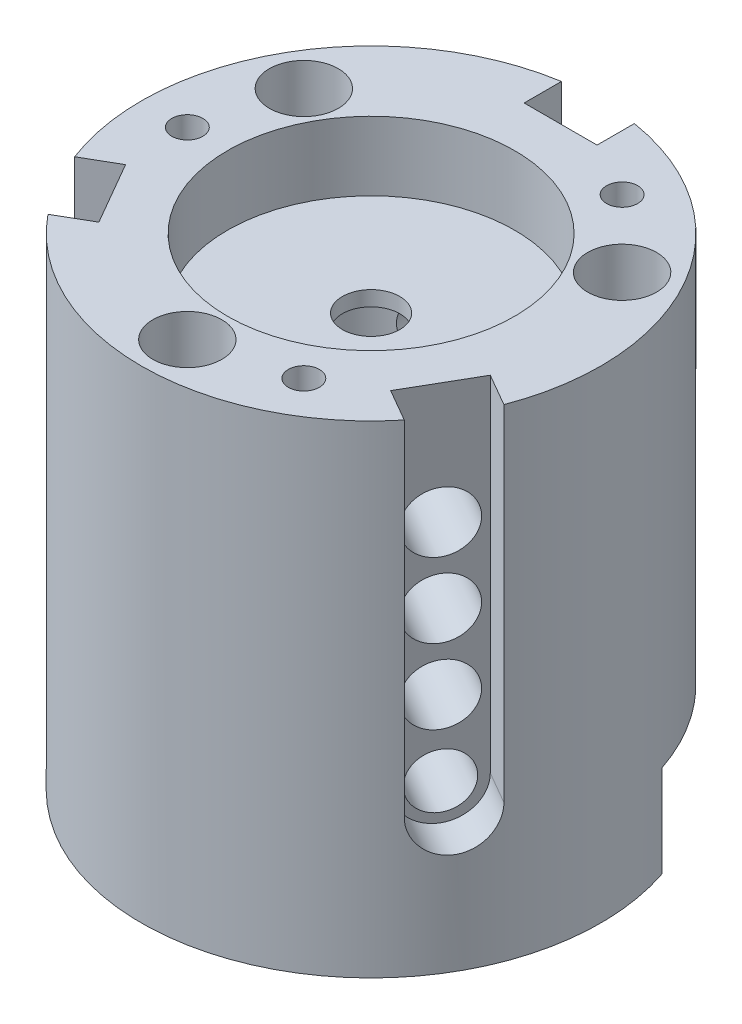
SolidWorks part; units mm, degrees
ref_plane "Front Plane" through (0, 0, 0) normal (0, 0, 1) x (1, 0, 0)
ref_plane "Top Plane" through (0, 0, 0) normal (0, 1, 0) x (1, 0, 0)
ref_plane "Right Plane" through (0, 0, 0) normal (1, 0, 0) x (0, 0, -1)
sketch "Sketch1" plane through (0, 0, 0) normal (0, 1, 0) x (1, 0, 0)
  circle A0 centre (0, 0) radius 20
  dimension "D1" = 40
extrude "Boss-Extrude1" add sketch "Sketch1" along normal blind 42
sketch "Sketch2" plane through (0, 0, 0) normal (0, 1, 0) x (1, 0, 0)
  circle A0 centre (0, 0) radius 5.5
  dimension "D1" = 11
extrude "Cut-Extrude1" cut sketch "Sketch2" along normal blind 35
sketch "Sketch3" plane through (0, 42, 0) normal (0, 1, 0) x (1, 0, 0)
  circle A1 centre (0, -16) radius 3
  circle A2 centre (-13.8564, 8) radius 3
  circle A3 centre (13.8564, 8) radius 3
  point P7 (0, 0)
  dimension "D1" = 3
  dimension "D3" = 6
  dimension "D2" = 16
extrude "Cut-Extrude2" cut sketch "Sketch3" against normal blind 20
sketch "Sketch4" plane through (0, 42, 0) normal (0, 1, 0) x (1, 0, 0)
  circle A0 centre (0, 0) radius 2.5
  dimension "D1" = 5
extrude "Cut-Extrude3" cut sketch "Sketch4" against normal through all
sketch "Sketch6" plane through (0, 42, 0) normal (0, 1, 0) x (1, 0, 0)
  line L0 (8, 13.8564) -> (0, 0) construction
  line L1 (0, 0) -> (0, 12.1298) construction
  circle A0 centre (8, 13.8564) radius 1.3525
  circle A1 centre (8, -13.8564) radius 1.3525
  circle A2 centre (-16, 0) radius 1.3526
  point P12 (0, 0)
  dimension "D3" = 2.7051
  dimension "D1" = 30
  dimension "D2" = 16
  dimension "D4" = 3
extrude "Cut-Extrude5" cut sketch "Sketch6" against normal blind 10
ref_axis "Axis1" through (0, -2, 0) along (0, 1, 0)
ref_plane "Plane1" through (0, 0, 0) normal (0.866, 0, -0.5) x (0, 1, 0)
ref_plane "Plane2" through (-17.3205, 0, 10) normal (0.866, 0, -0.5) x (0, 1, 0)
sketch "Sketch8" plane through (-17.3205, 0, 10) normal (0.866, 0, -0.5) x (0, 1, 0)
  line L0 (-2, 0) -> (42, 0) construction
  line L1 (42, -20) -> (42, 20) construction
  line L2 (42, 0) -> (12, 0) construction
  line L3 (42, -3.175) -> (12, -3.175)
  line L4 (42, 3.175) -> (12, 3.175)
  arc A1 (42, -3.175) -> (42, 3.175) centre (42, 0) ccw
  arc A2 (12, 3.175) -> (12, -3.175) centre (12, 0) ccw
  point P6 (27, 0)
  dimension "D1" = 3.175
  dimension "D2" = 0
  dimension "D3" = 30
extrude "Cut-Extrude6" cut sketch "Sketch8" along normal blind 3.5
sketch "Sketch9" plane through (-14.2894, 0, 8.25) normal (-0.866, 0, 0.5) x (0.5, 0, 0.866)
  line L1 (0, -2) -> (0, 42) construction
  circle A0 centre (0, 31.5) radius 2.625
  circle A1 centre (0, 25) radius 2.625
  circle A2 centre (0, 18.5) radius 2.625
  circle A3 centre (0, 12) radius 2.625
  arc A4 (-3.175, 12) -> (3.175, 12) centre (0, 12) ccw construction
  circle A5 centre (0, 12) radius 2.375
  dimension "D1" = 5.25
  dimension "D5" = 4.75
  dimension "D2" = 6.5
  dimension "D4" = 6.5
  dimension "D3" = 4
extrude "Cut-Extrude7" cut sketch "Sketch9" against normal up to surface (16.5 mm away) contours A2 | A1 | A0 region at (-14.2894, 31.5, 8.25) region at (-14.2894, 25, 8.25) region at (-14.2894, 18.5, 8.25) up to plane "Plane1"
sketch "Sketch12" plane through (-14.2894, 0, 8.25) normal (-0.866, 0, 0.5) x (0.5, 0, 0.866)
  circle A0 centre (0, 12) radius 2.375
  dimension "D1" = 4.75
extrude "Cut-Extrude9" cut sketch "Sketch12" against normal blind 6.35
pattern_circular "CirPattern1" count 3 over 360 about axis through (0, 42, 0) along (0, -1, 0) of "Cut-Extrude6", "Cut-Extrude7", "Cut-Extrude9" reverse direction yes
sketch "Sketch10" plane through (0, 42, 0) normal (0, 1, 0) x (1, 0, 0)
  circle A0 centre (0, 0) radius 12.5
  circle M6 centre (0, 0) radius 2.5
  dimension "D1" = 25
extrude "Cut-Extrude8" cut sketch "Sketch10" against normal blind 6 contours A0 M6 region at (-12.1464, 42, 0)
sketch "Sketch14" plane through (0, 0, 0) normal (0, -1, 0) x (1, 0, 0)
  line L0 (0, -22) -> (0, 22) construction
  line L1 (21.3319, -25.2723) -> (6.35, -25.2723)
  line L2 (21.3319, -25.2723) -> (21.3319, -6.35)
  line L3 (21.3319, -6.35) -> (9.525, -6.35)
  line L4 (6.35, -25.2723) -> (6.35, -9.525)
  line L5 (21.3319, -25.2723) -> (6.35, -6.35) construction
  line L6 (21.3319, -6.35) -> (6.35, -25.2723) construction
  line L7 (-21.3319, -6.35) -> (-6.35, -25.2723) construction
  line L8 (-21.3319, -25.2723) -> (-6.35, -6.35) construction
  line L9 (-6.35, -25.2723) -> (-6.35, -9.525)
  line L10 (-21.3319, -6.35) -> (-9.525, -6.35)
  line L11 (-21.3319, -25.2723) -> (-21.3319, -6.35)
  line L12 (-21.3319, -25.2723) -> (-6.35, -25.2723)
  arc A0 (9.525, -6.35) -> (6.35, -9.525) centre (9.525, -9.525) ccw
  arc A1 (-9.525, -6.35) -> (-6.35, -9.525) centre (-9.525, -9.525) cw
  point P0 (13.841, -15.8112)
  point P17 (-13.841, -15.8112)
  dimension "D1" = 3.175
  dimension "D2" = 12.7
  dimension "D3" = 6.35
extrude "Cut-Extrude10" cut sketch "Sketch14" against normal blind 8
sketch "Sketch15" plane through (6.35, 0, 0) normal (1, 0, 0) x (0, 0, -1)
  line L0 (9.525, 0) -> (18.9652, 0) construction
  line L1 (18.9652, 8) -> (18.9652, 0) construction
  circle A0 centre (14.2451, 4) radius 1.5875
  point P2 (14.2451, 0)
  point P3 (18.9652, 4)
  dimension "D1" = 3.175
extrude "Cut-Extrude11" cut sketch "Sketch15" against normal through all
sketch "Sketch16" plane through (0, 42, 0) normal (0, 1, 0) x (1, 0, 0)
  line L0 (0, 0) -> (-8, 13.8564) construction
  line L1 (0, 0) -> (0, 12.5) construction
  circle A0 centre (-8, 13.8564) radius 2.3813
  circle A1 centre (0, 0) radius 12.5 construction
  circle A2 centre (16, 0) radius 2.3813
  circle A3 centre (-8, -13.8564) radius 2.3813
  point P13 (0, 0)
  dimension "D2" = 4.7625
  dimension "D1" = 16
  dimension "D3" = 30
  dimension "D4" = 3
chamfer "Chamfer1" distance 3.5 angle 31 1 edges at (0, 35, 5.5) first distance on face at (0, 35, 2.5)
